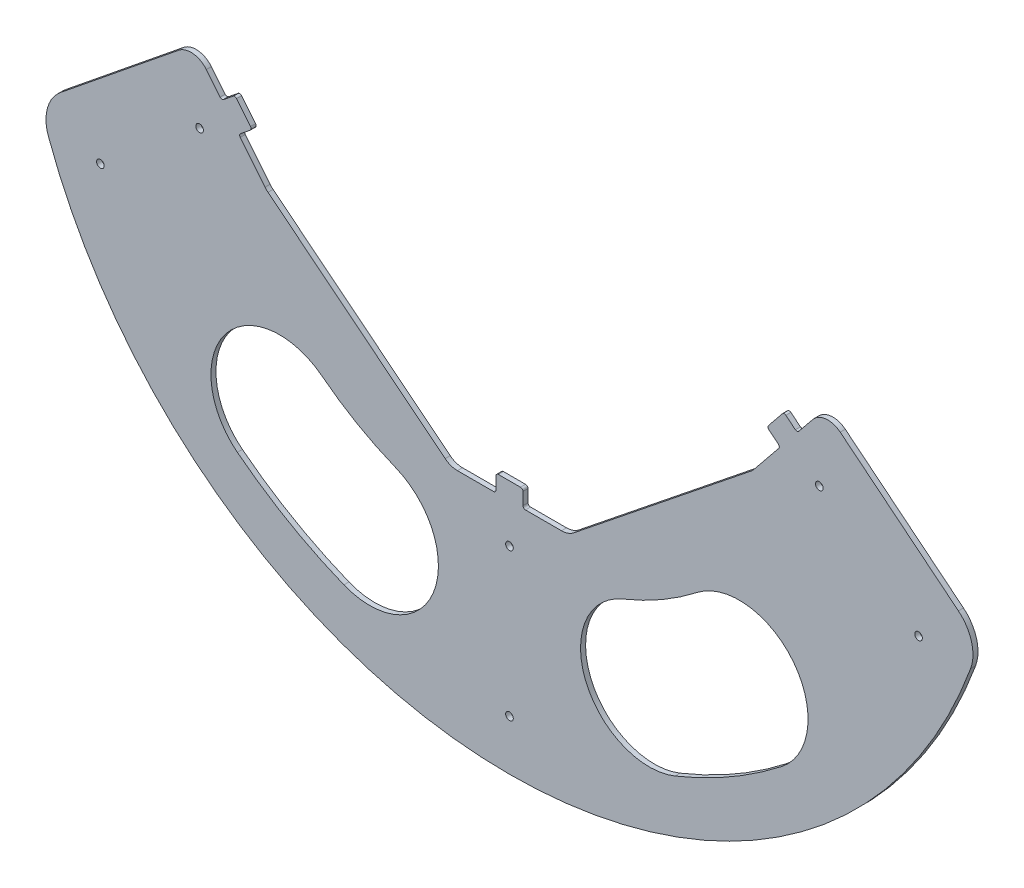
SolidWorks part; units mm, degrees
material "6061 Alloy"
ref_plane "Front Plane" through (0, 0, 0) normal (0, 0, 1) x (1, 0, 0)
ref_plane "Top Plane" through (0, 0, 0) normal (0, 1, 0) x (1, 0, 0)
ref_plane "Right Plane" through (0, 0, 0) normal (1, 0, 0) x (0, 0, -1)
sketch "Sketch1" plane through (0, 0, 0) normal (0, 0, 1) x (1, 0, 0)
  line L0 (0, 0) -> (-120.65, -208.9719) construction
  line L1 (-120.65, -208.9719) -> (120.65, -208.9719) construction
  line L2 (120.65, -208.9719) -> (0, 0) construction
  line L3 (0, 0) -> (0, -208.9719) construction
  line L4 (-148.5591, -190.147) -> (0, 0) construction
  line L5 (0, 0) -> (-90.3926, -223.7295) construction
  line L6 (-38.1, -185.1511) -> (-38.1, 42.5239) construction
  line L7 (50001.5956, 76.9937) -> (-50001.5956, 76.9937) construction
  line L8 (0, -164.3062) -> (50000, -164.3062) construction
  line L9 (0, 76.9938) -> (-95.25, 76.9938) construction
  line L10 (-95.25, 76.9938) -> (-272.327, -66.4004) construction
  line L11 (-151.7718, -64.4909) -> (-39009.0699, -31530.5105) construction
  line L12 (-157.1539, -68.8492) -> (-203.9652, -11.0421) construction
  line L13 (-186.0543, -33.1602) -> (-175.0648, -46.7311) construction
  line L14 (-175.0648, -46.7311) -> (-166.4288, -39.7378)
  line L15 (-186.0543, -33.1602) -> (-177.4183, -26.1669)
  line L16 (-177.4183, -26.1669) -> (-166.4288, -39.7378)
  line L17 (-303.8907, -91.9602) -> (-203.9652, -11.0421)
  line L18 (-8.7312, -164.3062) -> (8.7313, -164.3062) construction
  line L19 (-8.7312, -164.3062) -> (-8.7312, -153.1938)
  line L20 (-8.7312, -153.1938) -> (8.7313, -153.1938)
  line L21 (8.7313, -164.3062) -> (8.7313, -153.1938)
  line L22 (-203.9652, -11.0421) -> (-186.0543, -33.1602)
  line L23 (-175.0648, -46.7311) -> (-157.1539, -68.8492)
  line L24 (-157.1539, -68.8492) -> (-38.1, -164.3062)
  line L25 (-38.1, -164.3062) -> (-8.7312, -164.3062)
  line L26 (0, -208.9719) -> (0, -317.5) construction
  line L27 (303.8907, -91.9602) -> (203.9652, -11.0421)
  line L28 (203.9652, -11.0421) -> (186.0543, -33.1602)
  line L29 (186.0543, -33.1602) -> (177.4183, -26.1669)
  line L30 (177.4183, -26.1669) -> (166.4288, -39.7378)
  line L31 (175.0648, -46.7311) -> (166.4288, -39.7378)
  line L32 (175.0648, -46.7311) -> (157.1539, -68.8492)
  line L33 (157.1539, -68.8492) -> (38.1, -164.3062)
  line L34 (38.1, -164.3062) -> (8.7313, -164.3062)
  circle A0 centre (0, 0) radius 19.8438 construction
  arc A1 (-148.5591, -190.147) -> (-90.3926, -223.7295) centre (0, 0) ccw construction
  arc A2 (-175.9253, -225.1741) -> (-107.0438, -264.9428) centre (0, 0) ccw
  arc A3 (-121.193, -155.1199) -> (-73.7413, -182.5161) centre (0, 0) ccw
  arc A4 (-121.193, -155.1199) -> (-175.9253, -225.1741) centre (-148.5591, -190.147) ccw
  arc A5 (-107.0438, -264.9428) -> (-73.7413, -182.5161) centre (-90.3926, -223.7295) ccw
  arc A6 (148.5591, -190.147) -> (90.3926, -223.7295) centre (0, 0) cw construction
  arc A7 (175.9253, -225.1741) -> (107.0438, -264.9428) centre (0, 0) cw
  arc A8 (121.193, -155.1199) -> (73.7413, -182.5161) centre (0, 0) cw
  arc A9 (121.193, -155.1199) -> (175.9253, -225.1741) centre (148.5591, -190.147) cw
  arc A10 (107.0438, -264.9428) -> (73.7413, -182.5161) centre (90.3926, -223.7295) cw
  arc A11 (-303.8907, -91.9602) -> (303.8907, -91.9602) centre (0, 0) ccw
  point P8 (-120.65, -208.9719)
  point P18 (120.65, -208.9719)
  point P27 (0, 76.9938)
  point P28 (0, 19.8438)
  point P33 (-38.1, 27.5587)
  point P39 (-157.1539, -68.8492)
  point P52 (0, -153.1938)
  dimension "D1" = 39.6875
  dimension "D5" = 44.45
  dimension "D15" = 31.75
  dimension "D2" = 30
  dimension "D3" = 241.3
  dimension "D4" = 8
  dimension "D6" = 38.1
  dimension "D7" = 57.15
  dimension "D8" = 241.3
  dimension "D9" = 95.25
  dimension "D10" = 39
  dimension "D11" = 74.3839
  dimension "D12" = 153.1937
  dimension "D13" = 11.1125
  dimension "D14" = 17.4625
base flange "Base-Flange1" sketch "Sketch1" thickness 3.2639 reverse thickness direction no parameters "D1"=1.27
sketch "Sketch6" plane through (0, 0, 0) normal (0, 0, 1) x (1, 0, 0)
  line L0 (-171.9235, -32.9523) -> (-290.2236, -128.7498) construction
  line L1 (-166.4288, -39.7378) -> (-177.4183, -26.1669) construction
  line L2 (-186.0543, -33.1602) -> (-203.9652, -11.0421) construction
  line L3 (8.7313, -153.1938) -> (-8.7312, -153.1938) construction
  line L4 (0, -153.1938) -> (0, -317.5) construction
  line L5 (-8.7312, -164.3062) -> (-38.1, -164.3062) construction
  arc A0 (-303.8907, -91.9602) -> (303.8907, -91.9602) centre (0, 0) ccw construction
  point P11 (-200.2991, -55.9304)
  point P12 (-264.4525, -107.8808)
  point P13 (0, -189.7062)
  point P14 (0, -284.9563)
  point P19 (264.4525, -107.8808)
  point P20 (200.2991, -55.9304)
  dimension "D1" = 25.4
  dimension "D2" = 82.55
  dimension "D3" = 25.4
  dimension "D4" = 95.25
hole_wizard "#10 (0.1935) Diameter Hole1" positions "Sketch7" profile "Sketch8" hole size "#10" standard "ANSI Inch" end condition up to next
sketch "Sketch7" plane through (0, 0, 0) normal (0, 0, 1) x (1, 0, 0)
  point P0 (-200.2991, -55.9304)
  point P3 (-264.4525, -107.8808)
  point P6 (0, -189.7062)
  point P9 (0, -284.9563)
  point P12 (200.2991, -55.9304)
  point P15 (264.4525, -107.8808)
sketch "Sketch8" plane through (-200.2991, -55.9304, 0) normal (1, 0, 0) x (0, -1, 0)
  line L0 (0, 0) -> (0, 3.2639)
  line L1 (0, 3.2639) -> (2.4574, 3.2639)
  line L2 (2.4574, 3.2639) -> (2.4574, 0)
  line L5 (2.4574, 0) -> (0, 0)
  line L11 (0, -6.35) -> (0, 107.95) construction
  dimension "Thru Hole Dia." = 4.9149
  dimension "Thru Hole Depth" = 3.2639
sketch "Sketch9" [suppressed] plane through (0, 0, 0) normal (0, 0, 1) x (1, 0, 0)
  point P0 (31.75, -259.5563)
  point P1 (-31.75, -259.5563)
  point P2 (0, -284.9563)
  dimension "D1" = 31.75
  dimension "D2" = 25.4
  dimension "D3" = 31.75
hole_wizard "1/2 Clearance Hole1" [suppressed] positions "Sketch10" profile "Sketch11" hole size "1/2" standard "ANSI Inch"
sketch "Sketch10" [suppressed] plane through (0, 0, 0) normal (0, 0, 1) x (1, 0, 0)
  point P0 (31.75, -259.5563)
  point P3 (-31.75, -259.5563)
sketch "Sketch11" [suppressed] plane through (31.75, -259.5563, 0) normal (1, 0, 0) x (0, -1, 0)
  line L0 (0, 0) -> (0, 3.2639)
  line L1 (0, 3.2639) -> (6.7462, 3.2639)
  line L2 (6.7462, 3.2639) -> (6.7462, 0)
  line L5 (6.7462, 0) -> (0, 0)
  line L11 (0, -6.35) -> (0, 107.95) construction
  dimension "Thru Hole Dia." = 13.4925
  dimension "Thru Hole Depth" = 3.2639
fillet "Fillet1" radius 1.5875 12 edges at (186.0543, -33.1602, -1.632) (-8.7312, -164.3062, -1.632) (177.4183, -26.1669, -1.632) (175.0648, -46.7311, -1.632) (166.4288, -39.7378, -1.632) (8.7313, -164.3062, -1.632) (8.7313, -153.1938, -1.632) (-8.7312, -153.1938, -1.632) (-175.0648, -46.7311, -1.632) (-166.4288, -39.7378, -1.632) (-177.4183, -26.1669, -1.632) (-186.0543, -33.1602, -1.632)
fillet "Fillet2" radius 12.7 6 edges at (-203.9652, -11.0421, -1.632) (-157.1539, -68.8492, -1.632) (-38.1, -164.3062, -1.632) (38.1, -164.3062, -1.632) (203.9652, -11.0421, -1.632) (157.1539, -68.8492, -1.632)
fillet "Fillet3" radius 25.4 2 edges at (-303.8907, -91.9602, -1.632) (303.8907, -91.9602, -1.632)
sketch "Bend-Lines1" [suppressed] plane through (0, 0, 0) normal (0, 1, 0) x (1, 0, 0)
sketch "Bounding-Box1" [suppressed] plane through (0, 0, 0) normal (0, 1, 0) x (1, 0, 0)
sheet metal parameters "Sheet-Metal1" thickness 3.2639 parameters "D1"=1.27
flat pattern "Flat-Pattern1" [suppressed]
sketch "Bend-Lines2" plane through (0, 0, 0) normal (0, 1, 0) x (1, 0, 0)
sketch3d "Bounding-Box2" [suppressed]
  line L0 (-303.8907, -317.5, 0) -> (303.8907, -317.5, 0) construction
  line L1 (-303.8907, -7.0976, 0) -> (303.8907, -7.0976, 0) construction
  line L2 (-303.8907, -317.5, 0) -> (-303.8907, -7.0976, 0) construction
  line L3 (303.8907, -317.5, 0) -> (303.8907, -7.0976, 0) construction
sheet metal parameters "Sheet-Metal2" thickness 3.2639 parameters "D1"=1.27
flat pattern "Flat-Pattern1"
sketch "Bend-Lines2" plane through (0, 0, 0) normal (0, 1, 0) x (1, 0, 0)
sketch3d "Bounding-Box2" [suppressed]
  line L0 (-299.6228, -16.2042, 0) -> (299.6228, -16.2043, 0) construction
  line L1 (-299.6229, -317.4999, 0) -> (299.6228, -317.5, 0) construction
  line L2 (-299.6228, -16.2042, 0) -> (-299.6229, -317.4999, 0) construction
  line L3 (299.6228, -16.2043, 0) -> (299.6228, -317.5, 0) construction
sheet metal parameters "Sheet-Metal17" thickness 3.2639 parameters "D1"=1.27
flat pattern "Flat-Pattern1"
sketch "Bend-Lines2" plane through (0, 0, 0) normal (0, 1, 0) x (1, 0, 0)
sketch3d "Bounding-Box2" [suppressed]
  line L0 (-299.6228, -12.2597, 0) -> (299.6228, -12.2598, 0) construction
  line L1 (-299.6229, -317.4999, 0) -> (299.6228, -317.5, 0) construction
  line L2 (-299.6228, -12.2597, 0) -> (-299.6229, -317.4999, 0) construction
  line L3 (299.6228, -12.2598, 0) -> (299.6228, -317.5, 0) construction
